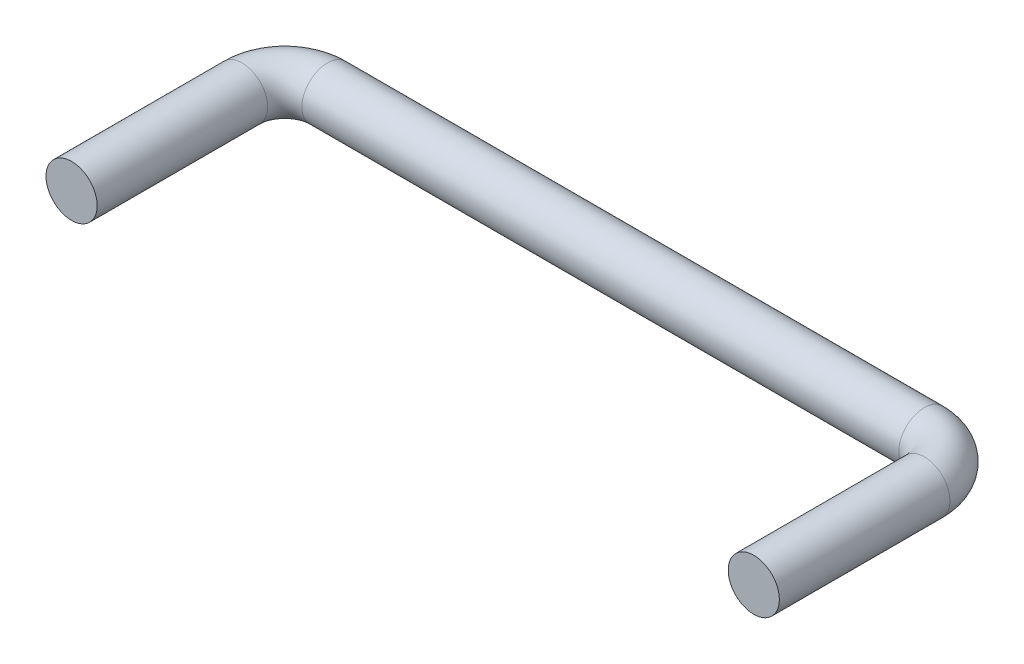
SolidWorks part; units mm, degrees
material "PS Średni/wysoki przepływ"
ref_plane "Płaszczyzna przednia" through (0, 0, 0) normal (0, 0, 1) x (1, 0, 0)
ref_plane "Płaszczyzna górna" through (0, 0, 0) normal (0, 1, 0) x (1, 0, 0)
ref_plane "Płaszczyzna prawa" through (0, 0, 0) normal (1, 0, 0) x (0, 0, -1)
sketch "Szkic1" plane through (0, 0, 0) normal (0, 1, 0) x (1, 0, 0)
  line L6 (-100, -30) -> (-100, -50)
  line L7 (-20, -30) -> (-20, -50)
  line L8 (-95, -25) -> (-25, -25)
  arc A6 (-25, -25) -> (-20, -30) centre (-25, -30) cw
  arc A7 (-95, -25) -> (-100, -30) centre (-95, -30) ccw
  point P0 (-60, -25)
  point P46 (-20, -25)
  point P49 (-100, -25)
  dimension "D1" = 20
  dimension "D2" = 20
  dimension "D3" = 80
ref_plane "Płaszczyzna1" through (-100, 0, 50) normal (0, 0, -1) x (-1, 0, 0)
sketch "Szkic3" plane through (-100, 0, 50) normal (0, 0, -1) x (-1, 0, 0)
  circle A0 centre (0, 0) radius 3
  dimension "D1" = 6
sweep "Wyciągnięcie po ścieżce4" add profiles "Szkic3" path "Szkic1"
ref_axis "Oś1" through (-127.5334, 0, 25) along (1, 0, 0)
ref_point "Punkt1"
